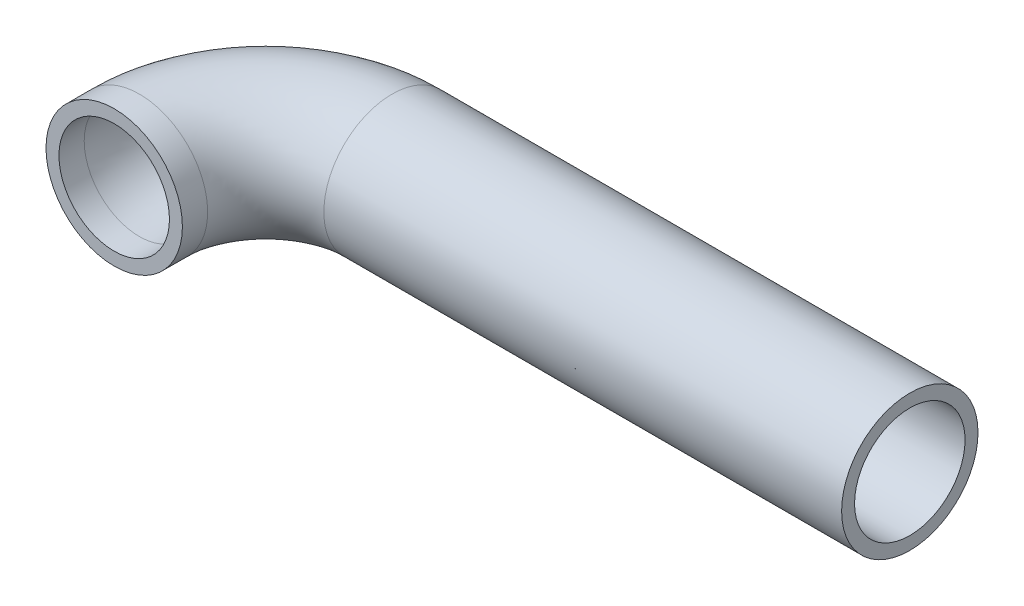
SolidWorks part; units mm, degrees
ref_plane "Front Plane" through (0, 0, 0) normal (0, 0, 1) x (1, 0, 0)
ref_plane "Top Plane" through (0, 0, 0) normal (0, 1, 0) x (1, 0, 0)
ref_plane "Right Plane" through (0, 0, 0) normal (1, 0, 0) x (0, 0, -1)
sketch "Sketch1" plane through (0, 0, 0) normal (0, 0, 1) x (1, 0, 0)
  circle A0 centre (0, 0) radius 5.5562
  circle A1 centre (0, 0) radius 6.858
  dimension "D1" = 11.1125
  dimension "D2" = 13.716
sketch "Sketch2" plane through (0, 0, 0) normal (0, 1, 0) x (1, 0, 0)
  line L0 (0, 0) -> (0, 2.54)
  line L1 (12.7, 15.24) -> (64.77, 15.24)
  arc A0 (0, 2.54) -> (12.7, 15.24) centre (12.7, 2.54) cw
  dimension "D2" = 12.7
  dimension "D1" = 2.54
  dimension "D3" = 52.07
sweep "Sweep1" add profiles "Sketch1" path "Sketch2"
